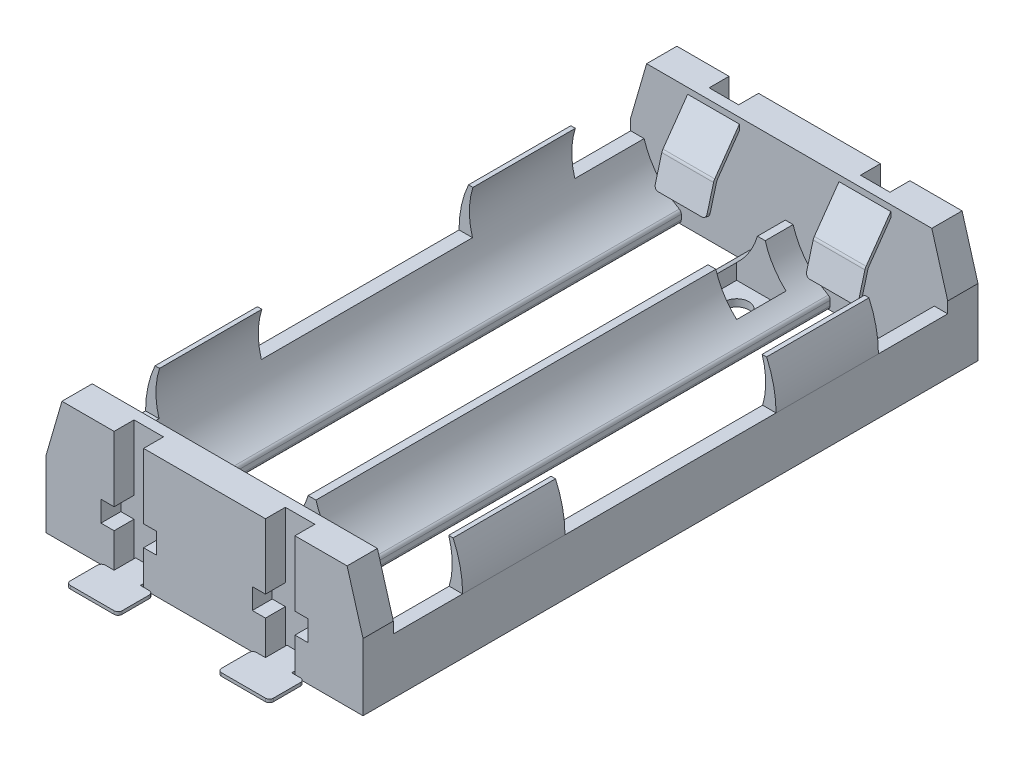
SolidWorks part; units mm, degrees
note: The reader was unsure of these and kept them because the rebuilt part matched: shared geometry of "Skica1<3>", "Skica1<4>", "Skica5<3>", "Skica10<4>".
ref_plane "Přední rovina" through (0, 0, 0) normal (0, 0, 1) x (1, 0, 0)
ref_plane "Horní rovina" through (0, 0, 0) normal (0, 1, 0) x (1, 0, 0)
ref_plane "Pravá rovina" through (0, 0, 0) normal (1, 0, 0) x (0, 0, -1)
sketch "Skica1" plane through (0, 0, 0) normal (0, 0, 1) x (1, 0, 0)
  line L0 (-19.9, 5.65) -> (19.9, 5.65)
  line L1 (-19.9, -9.65) -> (19.9, -9.65)
  line L2 (-19.9, -9.65) -> (-19.9, 9.65)
  line L3 (-19.9, 9.65) -> (19.9, 9.65)
  line L4 (19.9, -9.65) -> (19.9, 9.65)
  line L5 (-19.9, -9.65) -> (19.9, 9.65) construction
  line L6 (-19.9, 9.65) -> (19.9, -9.65) construction
  line L7 (17.9, 5.65) -> (19.9, -1.25)
  line L8 (0, 0) -> (0, 19.2226) construction
  line L9 (-17.9, 5.65) -> (-19.9, -1.25)
  circle A0 centre (9.35, 0) radius 9.25
  circle A1 centre (-9.35, 0) radius 9.25
  point P1 (0, 0)
  dimension "D3" = 0.4
  dimension "D4" = 18.6
  dimension "D5" = 18.5
  dimension "D1" = 39.8
  dimension "D2" = 15.3
  dimension "D6" = 8.4
  dimension "D7" = 17.9
extrude "Přidat vysunutím1" add sketch "Skica1" along normal blind 3.8 contours A0 L0 L9 L2 L1 L4 L7 | L0 A0 | A1 L0
extrude "Přidat vysunutím2" add sketch "Skica1<3>" along normal blind 77.2 contours L0 A1 L9 L2 L1 L4 L7 A0
sketch "Skica1<3>" plane through (0, 0, 0) normal (0, 0, 1) x (1, 0, 0) same geometry as "Skica1"
extrude "Přidat vysunutím3" add sketch "Skica1<4>" against normal blind 3.8 from offset 77.2 contours L0 A1 L9 L2 L1 L4 L7 A0 | L0 A0 | A1 L0
sketch "Skica1<4>" plane through (0, 0, 0) normal (0, 0, 1) x (1, 0, 0) same geometry as "Skica1"
sketch "Skica2" plane through (0, 0, 0) normal (0, 1, 0) x (1, 0, 0)
  line L1 (28.6072, -38.6) -> (-37.7841, -38.6)
  line L2 (28.6072, -38.6) -> (28.6072, -80.2606)
  line L3 (28.6072, -80.2606) -> (-37.7841, -80.2606)
  line L4 (-37.7841, -38.6) -> (-37.7841, -80.2606)
  line L5 (-17.9, -77.2) -> (-17.9, 0)
  point P4 (-17.9, -38.6)
extrude "Odebrat vysunutím1" cut sketch "Skica2" against normal through all both and the other way through all
sketch "Skica3" plane through (0, 0, 38.6) normal (0, 0, 1) x (1, 0, 0)
  line L0 (19.9, -9.65) -> (-19.9, -9.65) construction
  line L1 (6.4057, -2.65) -> (-6.5998, -2.65)
  line L2 (6.4057, -2.65) -> (6.4057, 11.8437)
  line L3 (6.4057, 11.8437) -> (-6.5998, 11.8437)
  line L4 (-6.5998, -2.65) -> (-6.5998, 11.8437)
  line L6 (-23.9405, 2.85) -> (27.9521, 2.85)
  line L7 (-23.9405, 2.85) -> (-23.9405, 14.6908)
  line L8 (-23.9405, 14.6908) -> (27.9521, 14.6908)
  line L9 (27.9521, 2.85) -> (27.9521, 14.6908)
  dimension "D1" = 7
  dimension "D2" = 12.5
extrude "Odebrat vysunutím2" cut sketch "Skica3" along a picked direction on the side against the normal up to surface (34.8 mm away) contours L2 L3 L4 L1 | L9 L8 L7 L6
sketch "Skica4" plane through (19.9, 0, 0) normal (1, 0, 0) x (0, 0, -1)
  line L0 (-38.6, -9.65) -> (0, -9.65) construction
  line L1 (-3.8, 5.65) -> (-12.5, 5.65)
  line L2 (-3.8, 5.65) -> (-3.8, -2.65)
  line L3 (-3.8, -2.65) -> (-12.5, -2.65)
  line L4 (-12.5, 5.65) -> (-12.5, -2.65)
  line L5 (-40.5733, 11.1557) -> (-25.35, 11.1557)
  line L6 (-40.5733, 11.1557) -> (-40.5733, -2.65)
  line L7 (-40.5733, -2.65) -> (-25.35, -2.65)
  line L8 (-25.35, 11.1557) -> (-25.35, -2.65)
  line L9 (-38.6, -1.25) -> (-38.6, -9.65) construction
  dimension "D1" = 7
  dimension "D2" = 8.7
  dimension "D3" = 13.25
extrude "Odebrat vysunutím3" cut sketch "Skica4" against normal through all
sketch "Skica5" plane through (0, 0, 25.35) normal (0, 0, 1) x (1, 0, 0)
  line L0 (0, 0) -> (0, -11.3153) construction
  line L1 (18.15, 2.85) -> (18.7116, 2.85) construction
  line L3 (19.9, -2.65) -> (19.9, -1.25) construction
  circle A1 centre (6.5787, -2.65) radius 13.3213
  point P3 (18.8831, 2.85)
  point P4 (19.9, -2.65)
  line M4 (19.9, -2.65) -> (19.9, -1.25)
  line M5 (19.9, -1.25) -> (18.7116, 2.85)
extrude "Odebrat vysunutím4" cut sketch "Skica5" against normal up to surface (21.55 mm away) contours A1 M4 M5 up to face at (0, -2.03, 3.8)
extrude "Přidat vysunutím4" add sketch "Skica5<3>" against normal up to surface (12.85 mm away) contours A1 M5
sketch "Skica5<3>" plane through (0, 0, 25.35) normal (0, 0, 1) x (1, 0, 0) same geometry as "Skica5"
mirror "Zrcadlit1" about plane through (0, 0, 0) normal (1, 0, 0) of "Odebrat vysunutím4", "Přidat vysunutím4"
sketch "Skica6" plane through (0, 0, 0) normal (0, 0, -1) x (-1, 0, 0)
  line L0 (0, 0) -> (0, 14.9626) construction
  line L1 (17.9, 5.65) -> (-17.9, 5.65) construction
  line L2 (-11.35, 5.65) -> (-7.65, 5.65)
  line L3 (-11.35, 5.65) -> (-11.35, -9.65)
  line L4 (-11.35, -9.65) -> (-7.65, -9.65)
  line L5 (-7.65, 5.65) -> (-7.65, -9.65)
  line L6 (19.9, -9.65) -> (-19.9, -9.65) construction
  line L7 (-9.5, 5.65) -> (-9.5, -9.65) construction
  line L8 (-13, -5.15) -> (-6, -5.15)
  line L9 (-13, -5.15) -> (-13, -2.55)
  line L10 (-13, -2.55) -> (-6, -2.55)
  line L11 (-6, -5.15) -> (-6, -2.55)
  line L12 (9.5, 5.65) -> (9.5, -9.65) construction
  line L13 (6, -5.15) -> (6, -2.55)
  line L14 (13, -2.55) -> (6, -2.55)
  line L15 (13, -5.15) -> (13, -2.55)
  line L16 (13, -5.15) -> (6, -5.15)
  line L17 (7.65, 5.65) -> (7.65, -9.65)
  line L18 (11.35, -9.65) -> (7.65, -9.65)
  line L19 (11.35, 5.65) -> (11.35, -9.65)
  line L20 (11.35, 5.65) -> (7.65, 5.65)
  line M9 (17.9, 5.65) -> (-17.9, 5.65)
  line M12 (-19.9, -9.65) -> (19.9, -9.65)
  dimension "D1" = 3.7
  dimension "D2" = 7.65
  dimension "D3" = 7
  dimension "D4" = 2.6
  dimension "D5" = 4.5
extrude "Odebrat vysunutím5" cut sketch "Skica6" against normal blind 2.5 contours L3 L10 L5 M9 | L8 L3 L5 M12 | L19 L17 L14 M9 | L19 L16 L17 M12 | L10 L3 L8 L5 | L8 L11 L10 L5 | L10 L9 L8 L3
sketch "Skica7" plane through (0, -9.65, 0) normal (0, -1, 0) x (1, 0, 0)
  line L0 (11.35, 2.5) -> (7.65, 2.5) construction
  line L1 (11.15, 2.5) -> (7.85, 2.5)
  line L2 (11.15, 2.5) -> (11.15, -0.2)
  line L3 (11.15, -0.2) -> (7.85, -0.2)
  line L4 (7.85, 2.5) -> (7.85, -0.2)
  line L5 (9.5, 2.5) -> (9.5, -5.1291) construction
  line L6 (12.75, -0.2) -> (6.25, -0.2)
  line L7 (12.75, -0.2) -> (12.75, -4.6)
  line L8 (12.75, -4.6) -> (6.25, -4.6)
  line L9 (6.25, -0.2) -> (6.25, -4.6)
  line L10 (11.35, 2.5) -> (11.35, 0) construction
  line L11 (7.65, 2.5) -> (7.65, 0) construction
  line L12 (-7.65, 0) -> (7.65, 0) construction
  line M11 (7.65, 2.5) -> (11.35, 2.5)
  dimension "D1" = 3.3
  dimension "D2" = 6.5
  dimension "D3" = 4.6
  dimension "D4" = 0.2
extrude "Přidat vysunutím5" add sketch "Skica7" against normal blind 0.4 separate body contours L5 L4 L6 M11 | L1 L5 L3 L2 | L5 L6 L9 L8 | L3 L5 L8 L7 L6
fillet "Zaoblit1" radius 0.2 1 edges at (9.5, -9.65, 2.5)
combine bodies "Kombinovat3" operation type add bodies to combine 111 110
mirror "Zrcadlit4" about plane through (0, 0, 0) normal (1, 0, 0) of bodies 112
ref_plane "Rovina1" through (9.5, 0, 0) normal (1, 0, 0) x (0, 0, -1)
sketch "Skica8" plane through (9.5, 0, 0) normal (1, 0, 0) x (0, 0, -1)
  line L0 (-3.8, 4.9) -> (-7, 0.35)
  line L1 (-3.8, 5.65) -> (-3.8, -1.25) construction
  line L2 (-7, 0.35) -> (-8, -3.35)
  line L3 (-8, -3.35) -> (-7.6139, -3.4544)
  line L4 (-7.6139, -3.4544) -> (-6.6323, 0.1776)
  line L5 (-6.6323, 0.1776) -> (-3.8, 4.2047)
  line L6 (0, 5.65) -> (0, -1.25) construction
  line L7 (0, -9.65) -> (0, -1.25) construction
  line L8 (-3.8, 5.65) -> (0, 5.65) construction
  line L9 (-3.8, 4.2047) -> (-3.8, 4.9)
  dimension "D1" = 0.4
  dimension "D2" = 0.4
  dimension "D3" = 7
  dimension "D4" = 8
  dimension "D5" = 9
  dimension "D6" = 5.3
  dimension "D7" = 0.75
extrude "Přidat vysunutím6" add sketch "Skica8" along normal mid plane 6.5
fillet "Zaoblit2" radius 0.5 2 edges at (12.75, -3.4022, 7.8069) (6.25, -3.4022, 7.8069)
fillet "Zaoblit3" radius 1 2 edges at (9.5, 0.1776, 6.6323) (9.5, 0.35, 7)
mirror "Zrcadlit5" about plane through (0, 0, 0) normal (1, 0, 0) of bodies 114
fillet "Zaoblit4" radius 0.5 8 edges at (-6.25, -9.45, -4.6) (-6.25, -9.45, -0.2) (-12.75, -9.45, -0.2) (-12.75, -9.45, -4.6) (6.25, -9.45, -4.6) (6.25, -9.45, -0.2) (12.75, -9.45, -0.2) (12.75, -9.45, -4.6)
sketch "Skica9" plane through (0, 0, 38.6) normal (0, 0, 1) x (1, 0, 0)
  line L0 (0, 0) -> (0, 27.8289) construction
  line L1 (5.15, -11.7625) -> (13.55, -11.7625)
  line L2 (5.15, -11.7625) -> (5.15, -3.5277)
  line L3 (5.15, -3.5277) -> (13.55, -3.5277)
  line L4 (13.55, -11.7625) -> (13.55, -3.5277)
  line L5 (9.35, -3.5277) -> (9.35, -11.7625) construction
  line L6 (-9.35, -3.5277) -> (-9.35, -11.7625) construction
  line L7 (-13.55, -11.7625) -> (-13.55, -3.5277)
  line L8 (-5.15, -3.5277) -> (-13.55, -3.5277)
  line L9 (-5.15, -11.7625) -> (-5.15, -3.5277)
  line L10 (-5.15, -11.7625) -> (-13.55, -11.7625)
  arc M9 (18.2123, -2.65) -> (0.4877, -2.65) centre (9.35, 0) cw
  arc M11 (-0.4877, -2.65) -> (-18.2123, -2.65) centre (-9.35, 0) cw
  line M14 (-19.9, -9.65) -> (19.9, -9.65)
  dimension "D1" = 8.4
extrude "Odebrat vysunutím6" cut sketch "Skica9" along direction (0, 0, 1) on the side against the normal up to surface (34.8 mm away) contours L9 L7 M14 M11 | L4 L2 M14 M9
fillet "Zaoblit5" radius 0.5 8 edges at (5.15, -9.65, 21.2) (5.15, -8.2415, 21.2) (13.55, -9.65, 21.2) (13.55, -8.2415, 21.2) (-5.15, -9.65, 21.2) (-5.15, -8.2415, 21.2) (-13.55, -9.65, 21.2) (-13.55, -8.2415, 21.2)
sketch "Skica10" plane through (0, -2.65, 0) normal (0, 1, 0) x (1, 0, 0)
  line L0 (-7.65, 0) -> (7.65, 0) construction
  line L1 (-3.1, -13.5) -> (3.1, -13.5)
  line L2 (-3.1, -13.5) -> (-3.1, -7.3)
  line L3 (-3.1, -7.3) -> (3.1, -7.3)
  line L4 (3.1, -13.5) -> (3.1, -7.3)
  line L5 (-3.1, -13.5) -> (3.1, -7.3) construction
  line L6 (-3.1, -7.3) -> (3.1, -13.5) construction
  circle A0 centre (0, -10.4) radius 1.55
  point P0 (0, -10.4)
  dimension "D2" = 3.1
  dimension "D1" = 6.2
  dimension "D3" = 7.3
extrude "Odebrat vysunutím7" cut sketch "Skica10" against normal through all both and the other way through all contours A0
extrude "Odebrat vysunutím8" cut sketch "Skica10<4>" against normal blind 6.1
sketch "Skica10<4>" plane through (0, -2.65, 0) normal (0, 1, 0) x (1, 0, 0) same geometry as "Skica10"
mirror "Zrcadlit6" about plane through (0, -9.65, 38.6) normal (0, 0, -1) of bodies 120 115
